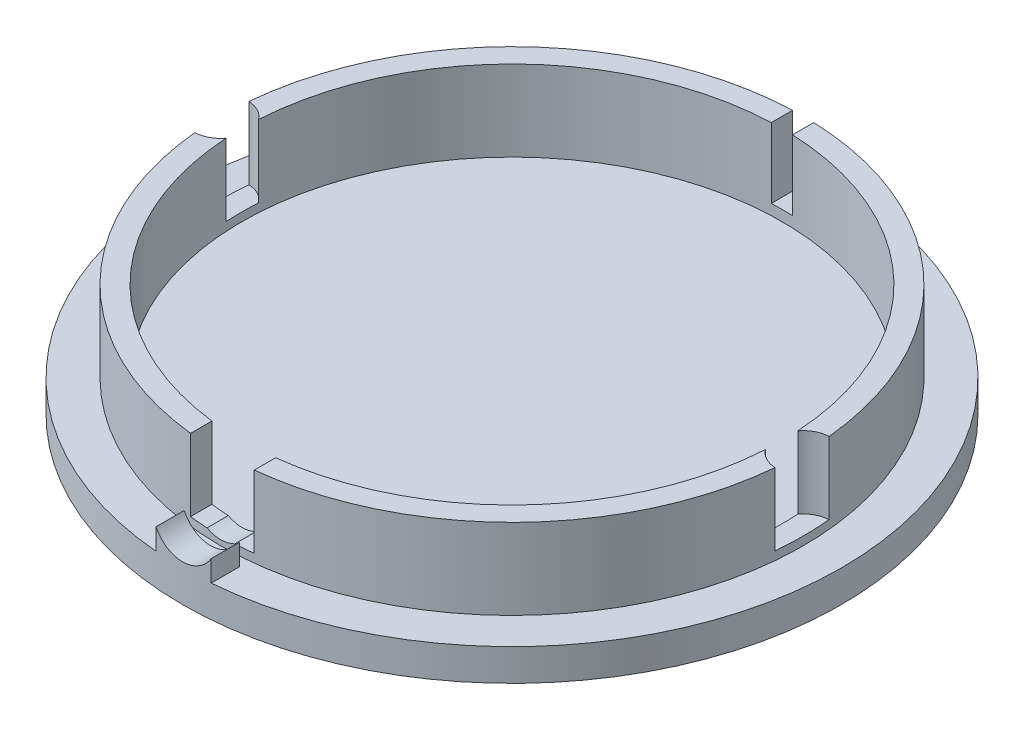
SolidWorks part; units mm, degrees
ref_plane "Front Plane" through (0, 0, 0) normal (0, 0, 1) x (1, 0, 0)
ref_plane "Top Plane" through (0, 0, 0) normal (0, 1, 0) x (1, 0, 0)
ref_plane "Right Plane" through (0, 0, 0) normal (1, 0, 0) x (0, 0, -1)
sketch "Sketch1" plane through (0, 0, 0) normal (0, 1, 0) x (1, 0, 0)
  circle A0 centre (0, 0) radius 31.06
  dimension "D1" = 62.12
extrude "Boss-Extrude1" add sketch "Sketch1" along normal blind 3
sketch "Sketch2" plane through (0, 3, 0) normal (0, 1, 0) x (1, 0, 0)
  circle A0 centre (0, 0) radius 27.46
  circle A1 centre (0, 0) radius 25.46
  circle A2 centre (0, 0) radius 31.06 construction
  dimension "D1" = 2
  dimension "D2" = 3.6
extrude "Boss-Extrude2" add sketch "Sketch2" along normal blind 7.6
sketch "Sketch4" plane through (0, 10.6, 0) normal (0, 1, 0) x (1, 0, 0)
  arc A0 (25.4144, -1.5226) -> (27.3416, -2.5472) centre (27.46, 0) ccw
  circle A1 centre (0, 0) radius 27.46 construction
  arc A2 (-27.3416, -2.5472) -> (-25.4144, -1.5226) centre (-27.46, 0) ccw
  circle A3 centre (0, 0) radius 25.46 construction
  arc A4 (-25.4144, 1.5226) -> (-25.4144, -1.5226) centre (0, 0) ccw
  arc A5 (-27.3416, 2.5472) -> (-27.3416, -2.5472) centre (0, 0) ccw
  arc A6 (25.4144, -1.5226) -> (25.4144, 1.5226) centre (0, 0) ccw
  arc A7 (27.3416, -2.5472) -> (27.3416, 2.5472) centre (0, 0) ccw
  arc A8 (-25.4144, 1.5226) -> (-27.3416, 2.5472) centre (-27.46, 0) ccw
  arc A9 (27.3416, 2.5472) -> (25.4144, 1.5226) centre (27.46, 0) ccw
  circle M1 centre (0, 0) radius 27.46
  circle M2 centre (0, 0) radius 25.46
  dimension "D1" = 5.1
  dimension "D2" = 5.1
extrude "Cut-Extrude1" cut sketch "Sketch4" against normal blind 6.8 contours A9 A0 M1 M2 | A4 A2 A5 A8 region at (26.5014, 10.6, 0)
sketch "Sketch5" plane through (0, 10.6, 0) normal (0, 1, 0) x (1, 0, 0)
  line L0 (0, -25.46) -> (0, -27.46)
  line L1 (3, -25.2826) -> (3, -27.2956)
  line L2 (-3, -25.2826) -> (-3, -27.2956)
  line L3 (3, -25.46) -> (3, -27.46) construction
  line L4 (-3, -25.46) -> (-3, -27.46) construction
  arc A0 (-25.4144, -1.5226) -> (25.4144, -1.5226) centre (0, 0) ccw construction
  arc A1 (-27.3416, -2.5472) -> (27.3416, -2.5472) centre (0, 0) ccw construction
  arc A3 (-3, -25.2826) -> (3, -25.2826) centre (0, 0) ccw
  arc A4 (-3, -27.2956) -> (3, -27.2956) centre (0, 0) ccw
  arc M2 (-27.3416, -2.5472) -> (27.3416, -2.5472) centre (0, 0) ccw
  arc M4 (25.4144, -1.5226) -> (-25.4144, -1.5226) centre (0, 0) cw
  dimension "D1" = 3
  dimension "D2" = 3
extrude "Cut-Extrude2" cut sketch "Sketch5" against normal blind 6.8 contours L2 L0 M4 M2 | L1 L0 M4 M2 region at (1.5016, 10.6, 26.403) region at (-1.5016, 10.6, 26.403)
sketch "Sketch7" plane through (0, 3, 0) normal (0, 1, 0) x (1, 0, 0)
  line L2 (2.6, -28.3014) -> (2.6, -30.951)
  line L3 (-2.6, -28.3014) -> (-2.6, -30.951)
  line L4 (3, -25.2826) -> (3, -27.2956) construction
  circle A0 centre (0, 0) radius 31.06 construction
  arc A1 (-2.6, -30.951) -> (2.6, -30.951) centre (0, 0) ccw
  arc A4 (-2.6, -28.3014) -> (2.6, -28.3014) centre (0, 0.0395) ccw
  dimension "D1" = 5.2
  dimension "D2" = 0.4
extrude "Boss-Extrude5" add sketch "Sketch7" along normal blind 7.6
ref_plane "Plane1" through (0, 0, 31.06) normal (0, 0, 1) x (1, 0, 0)
sketch "Sketch8" plane through (0, 0, 31.06) normal (0, 0, 1) x (1, 0, 0)
  line L0 (2.6, 10.6) -> (-2.6, 10.6) construction
  line L1 (2.6, 10.6) -> (-2.6, 10.6)
  line L2 (31.06, 3) -> (-31.06, 3) construction
  line L3 (2.6, 3) -> (-2.6, 3)
  line L4 (2.6, 10.6) -> (2.6, 3) construction
  line L5 (2.6, 10.6) -> (2.6, 3)
  line L6 (-2.6, 10.6) -> (-2.6, 3) construction
  line L7 (-2.6, 10.6) -> (-2.6, 3)
  line L8 (-2.6, 6.5) -> (2.6, 6.5)
  circle A0 centre (0, 6.5) radius 3
  dimension "D2" = 6
  dimension "D1" = 3.5
extrude "Cut-Extrude3" cut sketch "Sketch8" against normal blind 7.6 contours L7 A0 L5 L8 | L5 A0 L7 L8 | A0 L5 L1 L7 region at (0, 9.7737, 31.06) region at (0, 7.8162, 31.06) region at (0, 5.1838, 31.06)
sketch "Sketch9" plane through (0, 0, 0) normal (0, 0, 1) x (1, 0, 0)
  line L0 (25.4144, 10.6) -> (-25.4144, 10.6) construction
  line L1 (-1, 4) -> (1, 4)
  line L2 (-1, 4) -> (-1, 10.6)
  line L3 (-1, 6) -> (1, 6)
  line L4 (1, 4) -> (1, 10.6)
  line L5 (-1, 4) -> (1, 6) construction
  line L6 (-1, 6) -> (1, 4) construction
  line L7 (1, 10.6) -> (-1, 10.6)
  point P0 (0, 5)
  dimension "D1" = 5
  dimension "D2" = 2
  dimension "D3" = 2
extrude "Cut-Extrude4" cut sketch "Sketch9" against normal through all contours L1 L4 L3 L2 | L4 L7 L2 L3 region at (0, 5, 0) region at (0, 8.3, 0)
sketch "Sketch10" plane through (0, 3, 0) normal (0, 1, 0) x (1, 0, 0)
  line L2 (-0.7, 31.0521) -> (-0.7, 28.4424)
  line L3 (0.7, 31.0521) -> (0.7, 28.4424)
  line L5 (1, 27.4418) -> (1, 25.4404) construction
  arc A2 (2.6, -30.951) -> (-2.6, -30.951) centre (0, 0) ccw construction
  arc A3 (0.7, 31.0521) -> (-0.7, 31.0521) centre (0, 0) ccw
  arc A4 (0.7, 28.4424) -> (-0.7, 28.4424) centre (0, -0.009) ccw
  dimension "D1" = 1.4
  dimension "D2" = 0.3
extrude "Boss-Extrude6" add sketch "Sketch10" along normal blind 3.5
